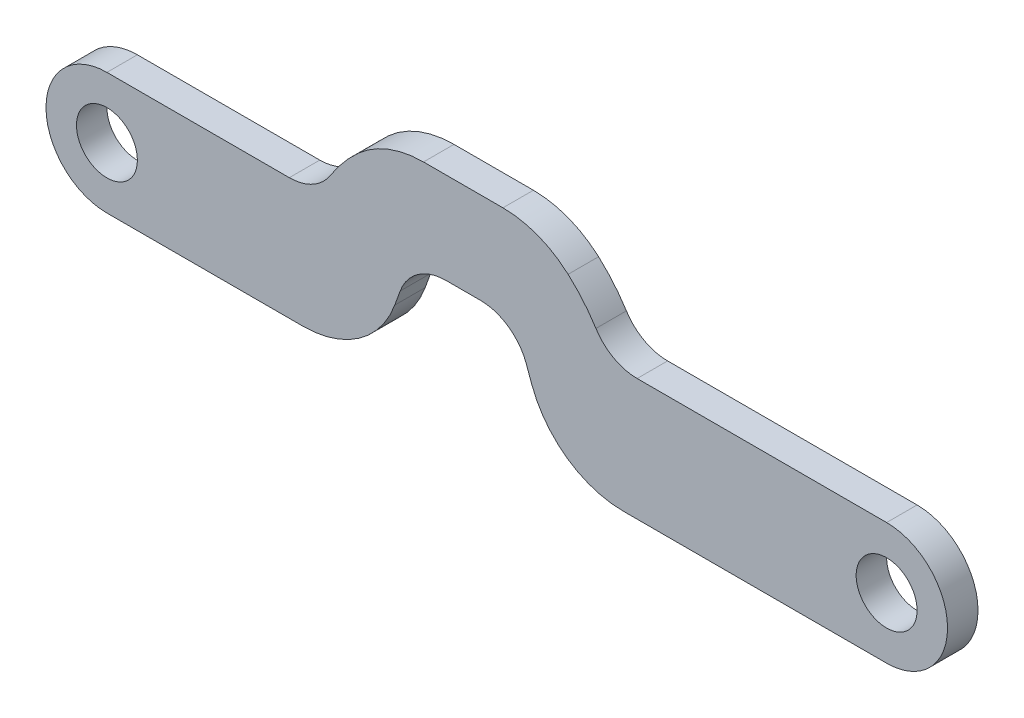
SolidWorks part; units mm, degrees
ref_plane "Спереди" through (0, 0, 0) normal (0, 0, 1) x (1, 0, 0)
ref_plane "Сверху" through (0, 0, 0) normal (0, 1, 0) x (1, 0, 0)
ref_plane "Справа" through (0, 0, 0) normal (1, 0, 0) x (0, 0, -1)
sketch "Эскиз1" plane through (0, 0, 0) normal (0, 0, 1) x (1, 0, 0)
  line L0 (0, 0) -> (-25.5979, 0)
  line L1 (-25.5979, -2) -> (0, -2)
  line L2 (-25.5979, 2) -> (0, 2)
  circle A0 centre (-25.5979, 0) radius 1
  circle A1 centre (0, 0) radius 1
  circle A2 centre (-25.5979, 0) radius 2
  circle A3 centre (0, 0) radius 2
  dimension "D1" = 25.5979
extrude "Бобышка-Вытянуть1" add sketch "Эскиз1" along normal mid plane 1 contours A3 L2 A2 L0 | A3 L0 A2 L1 | A2 A0 | A3 A1 region at (-12.7989, 1.0211, 0) region at (-24.2237, -1.3742, 0) region at (-12.7989, -1.0211, 0) region at (-1.3742, 1.3742, 0)
sketch "Sketch2" plane through (0, 0, 0) normal (0, 0, 1) x (1, 0, 0)
  line L0 (0, 0) -> (-13.9, 0)
  line L1 (-13.9, 2.15) -> (-13.9, 1.65)
  line L2 (-15.9203, 0.7353) -> (-16.9159, -2)
  line L3 (-11.8797, 0.7353) -> (-10.8841, -2)
  line L4 (-13.9, 0) -> (-13.9, -2)
  line L5 (-25.5979, -2) -> (0, -2) construction
  line L6 (-13.9, -2) -> (-19.127, -2)
  line L7 (-13.9, -2) -> (-4.4438, -2)
  line L8 (-18.7394, 1.7614) -> (-19.735, -0.9739)
  line L9 (-9.0606, 1.7614) -> (-8.065, -0.9739)
  line L10 (-13.9, 5.15) -> (-13.9, 4.65)
  line L11 (-13.9, 4.65) -> (-9.896, 4.65)
  line L12 (-13.9, 4.65) -> (-18.5901, 4.65)
  line L13 (-13.9, 1.65) -> (-12.0152, 1.65)
  line L14 (-13.9, 1.65) -> (-15.8325, 1.65)
  circle A0 centre (-13.9, 0) radius 2.15
  circle A1 centre (-13.9, 0) radius 5.15
  dimension "D2" = 4.3
  dimension "D3" = 3
  dimension "D4" = 3
  dimension "D5" = 3
extrude "Extrude1" add sketch "Sketch2" along normal mid plane 1 contours L0 A1 L11 L12 L6 L2 A0 L3 | L10 A1 L12 | L11 A1 L10 | L0 A0 L13 L14 L6 L4 | L13 A0 L1 | L1 A0 L14 region at (-14.2333, 0.1753, 0) region at (-11.6306, 0.4096, 0) region at (-13.374, 1.8521, 0) region at (-14.426, 1.8521, 0) region at (-13.0643, 4.8509, 0) region at (-14.7357, 4.8509, 0)
extrude "Extrude2" cut sketch "Sketch" against normal mid plane 1 contours L10 A1 L12 | L11 A1 L10 | L0 A0 L13 L14 L6 L4 | A0 L2 L6 | A0 L7 L3 L0 | L7 A0 L0 L4 | A0 L0 L3 region at (-12.9737, -0.8868, 0) region at (-11.7214, 0.1861, 0) region at (-14.2333, 0.1753, 0) region at (-11.7391, -1.3677, 0) region at (-16.0613, -1.3378, 0) region at (-13.0643, 4.8509, 0) region at (-14.7357, 4.8509, 0)
sketch "Sketch" plane through (0, 0, 0) normal (0, 0, 1) x (1, 0, 0) same geometry as "Sketch2"
fillet "Fillet2" radius 1.6 4 edges at (-9.1542, 2, 0) (-18.6458, 2, 0) (-12.5216, 1.65, 0) (-15.2784, 1.65, 0)
fillet "Fillet3" radius 3.2 4 edges at (-10.8841, -2, 0) (-16.9159, -2, 0) (-11.6864, 4.65, 0) (-16.1136, 4.65, 0)
